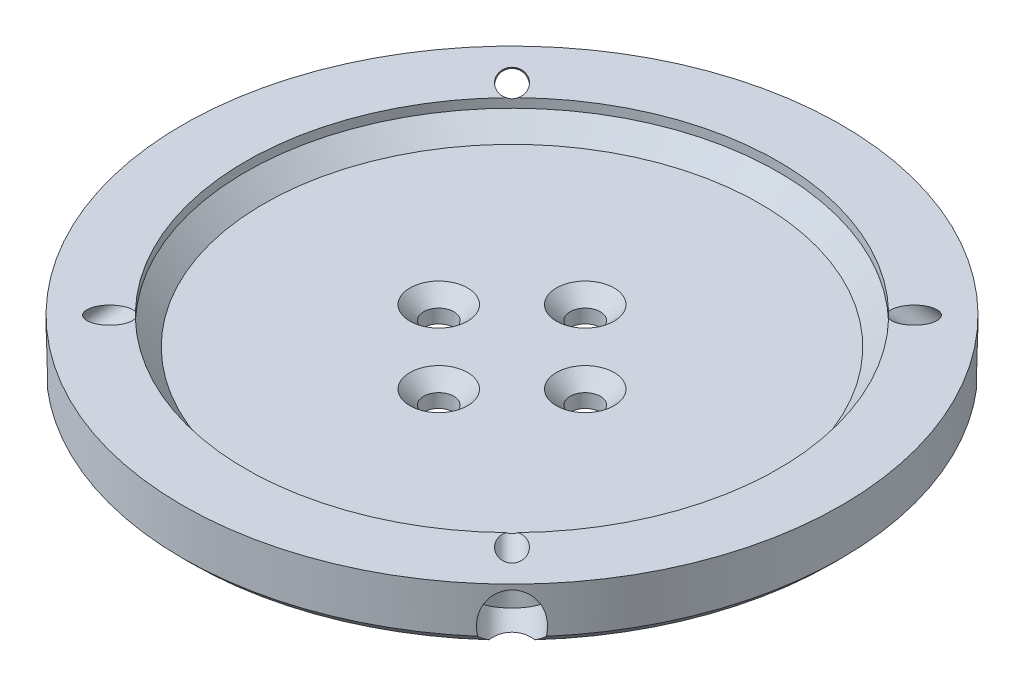
SolidWorks part; units mm, degrees
ref_plane "Front Plane" through (0, 0, 0) normal (0, 0, 1) x (1, 0, 0)
ref_plane "Top Plane" through (0, 0, 0) normal (0, 1, 0) x (1, 0, 0)
ref_plane "Right Plane" through (0, 0, 0) normal (1, 0, 0) x (0, 0, -1)
sketch "Sketch1" plane through (0, 0, 0) normal (0, 1, 0) x (1, 0, 0)
  circle A0 centre (0, 0) radius 36
  dimension "D1" = 72
extrude "Boss-Extrude1" add sketch "Sketch1" along normal mid plane 3
sketch "Sketch2" plane through (0, 1.5, 0) normal (0, 1, 0) x (1, 0, 0)
  circle A0 centre (0, 0) radius 8 construction
  circle A1 centre (0, 8) radius 1.5
  circle A2 centre (8, 0) radius 1.5
  circle A3 centre (0, -8) radius 1.5
  circle A4 centre (-8, 0) radius 1.5
  point P13 (0, 0)
  dimension "D1" = 16
  dimension "D2" = 3
  dimension "D3" = 4
hole_wizard "CSK for M3 Flat Head Machine Screw1" positions "Sketch3" profile "Sketch4" countersink size "M3" standard "ANSI Metric" end condition through all
sketch "Sketch3" plane through (0, 1.5, 0) normal (0, 1, 0) x (1, 0, 0)
  point P0 (0, 8)
  point P3 (-8, 0)
  point P6 (0, -8)
  point P9 (8, 0)
sketch "Sketch4" plane through (0, 1.5, -8) normal (1, 0, 0) x (0, 0, 1)
  line L0 (0, 0) -> (0, 3)
  line L1 (0, 3) -> (1.65, 3)
  line L2 (1.65, 3) -> (1.65, 1.5)
  line L3 (1.65, 1.5) -> (3.15, 0)
  line L5 (3.15, 0) -> (0, 0)
  line L6 (-1.65, 1.5) -> (-3.15, 0) construction
  line L11 (0, -6.35) -> (0, 107.95) construction
  dimension "Thru Hole Dia." = 3.3
  dimension "Thru Hole Depth" = 3
  dimension "Near C'Sink Dia." = 6.3
  dimension "Near C'Sink Angle" = 90
sketch "Sketch5" plane through (0, 1.5, 0) normal (0, 1, 0) x (1, 0, 0)
  circle A0 centre (0, 0) radius 29.1
  circle A1 centre (0, 0) radius 36
  circle A2 centre (0, 0) radius 36
  dimension "D2" = 58.2
  dimension "D1" = 0
extrude "Boss-Extrude2" add sketch "Sketch5" along normal blind 3
chamfer "Chamfer1" distance 1 angle 45 1 edges at (0, -1.5, 36)
ref_plane "Plane1" through (16.8294, -18.7709, -16.8294) normal (-0.5417, 0.6428, 0.5417) x (-0.7071, 0, -0.7071)
sketch "Sketch6" plane through (16.8294, -18.7709, -16.8294) normal (-0.5417, 0.6428, 0.5417) x (-0.7071, 0, -0.7071)
  circle A1 centre (0, -22.5) radius 1.1
  circle A2 centre (0, -22.5) radius 1.1
  dimension "D1" = 0
extrude "Cut-Extrude1" cut sketch "Sketch6" along normal through all
ref_plane "Plane2" through (15.7461, -17.4853, -15.7461) normal (-0.5417, 0.6428, 0.5417) x (-0.7071, 0, -0.7071)
sketch "Sketch7" plane through (16.8294, -18.7709, -16.8294) normal (-0.5417, 0.6428, 0.5417) x (-0.7071, 0, -0.7071)
  circle A1 centre (0, -22.5) radius 2.75
  circle A3 centre (0, -22.5) radius 1.1 construction
  dimension "D1" = 5.5
extrude "Cut-Extrude3" cut sketch "Sketch7" along normal blind 5.5 and the other way blind 4
ref_axis "Axis1" through (0, -2.6041, 0) along (0, 1, 0)
ref_plane "Plane3" through (0, 0, 0) normal (-0.7071, 0, -0.7071) x (0, 1, 0)
sketch "Sketch10" plane through (0, 0, 0) normal (-0.7071, 0, -0.7071) x (0, 1, 0)
  spline S0 degree 2 poles (3.9539, 36) (1.7943, 35.8671) (-0.5, 35.9021) knots 0 0 0 0.613993 0.613993 0.613993 weights 0.03325 0.034938 0.036627 construction
  spline S1 degree 2 poles (3.9539, 36) (1.7943, 35.8671) (-0.5, 35.9021) knots 0 0 0 0.613993 0.613993 0.613993 weights 0.03325 0.034938 0.036627
sketch "Sketch11" plane through (13.4324, -15.9397, -13.4324) normal (0.5417, -0.6428, -0.5417) x (0.8406, 0.4142, 0.3491)
  circle A0 centre (12.6632, -19.7004) radius 1.1 construction
  circle A1 centre (12.6632, -19.7004) radius 2.75
  circle A2 centre (12.6632, -19.7004) radius 2.75
  circle A3 centre (12.6632, -19.7004) radius 1.1
  dimension "D1" = 0
extrude "Boss-Extrude3" add sketch "Sketch11" along normal up to vertex up to point (25.4558, 3.9539, -25.4558)
hole_wizard "CSK for M2.5 Flat Head Machine Screw2" positions "Sketch12" profile "Sketch13" countersink size "M2.5" standard "ANSI Metric" end condition through all
sketch "Sketch12" plane through (13.5614, -16.0929, -13.5614) normal (0.5417, -0.6428, -0.5417) x (-0.8406, -0.4142, -0.3491)
  point P0 (-12.6632, 19.7004)
sketch "Sketch13" plane through (24.2059, 1.8473, -24.2059) normal (0.7071, 0, 0.7071) x (0.4545, 0.766, -0.4545)
  line L0 (0, 0) -> (0, 66.9683)
  line L1 (0, 66.9683) -> (1.35, 66.9683)
  line L2 (1.35, 66.9683) -> (1.35, 1.4)
  line L3 (1.35, 1.4) -> (2.75, 0)
  line L5 (2.75, 0) -> (0, 0)
  line L6 (-1.35, 1.4) -> (-2.75, 0) construction
  line L11 (0, -6.35) -> (0, 107.95) construction
  dimension "Thru Hole Dia." = 2.7
  dimension "Thru Hole Depth" = 66.9683
  dimension "Near C'Sink Dia." = 5.5
  dimension "Near C'Sink Angle" = 90
pattern_circular "CirPattern1" count 4 over 360 about axis through (0, -2.6041, 0) along (0, 1, 0) of "CSK for M2.5 Flat Head Machine Screw2", "Cut-Extrude3", "Cut-Extrude1", "Boss-Extrude3"
chamfer "Chamfer2" distance 2 angle 45 1 edges at (0, 1.5, 29.1)
